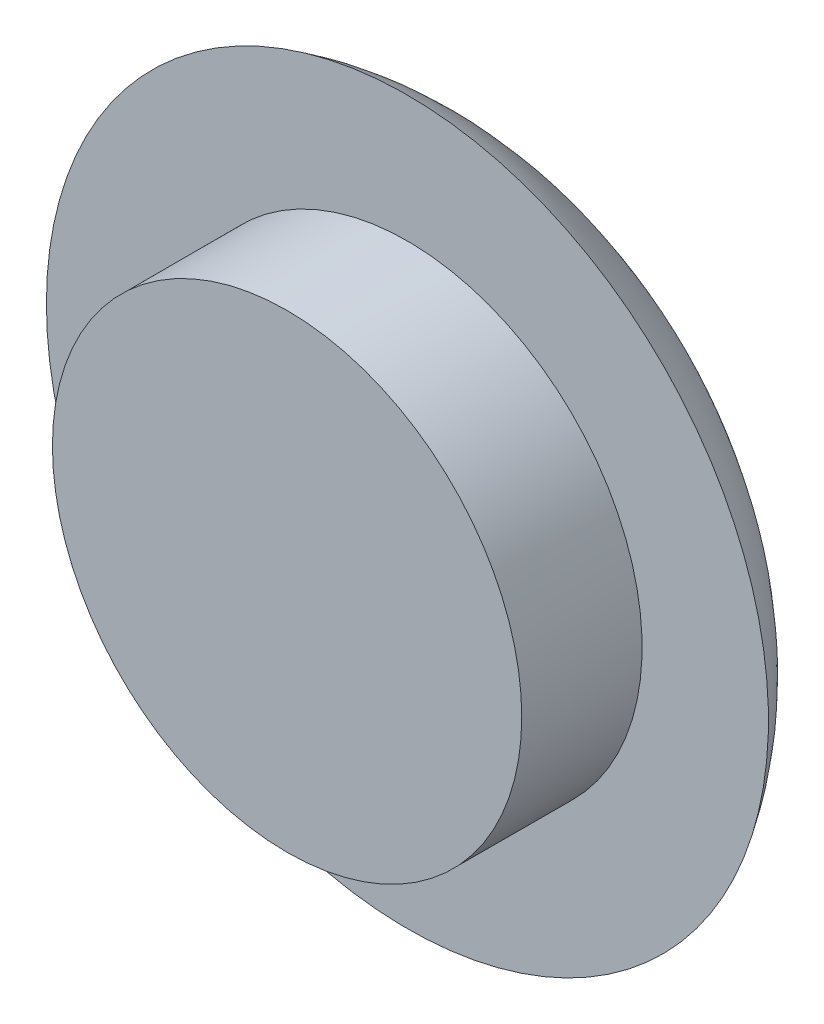
SolidWorks part; units mm, degrees
ref_plane "Front Plane" through (0, 0, 0) normal (0, 0, 1) x (1, 0, 0)
ref_plane "Top Plane" through (0, 0, 0) normal (0, 1, 0) x (1, 0, 0)
ref_plane "Right Plane" through (0, 0, 0) normal (1, 0, 0) x (0, 0, -1)
sketch "Sketch1" plane through (0, 0, 0) normal (0, 0, 1) x (1, 0, 0)
  circle A0 centre (0, 0) radius 2.925
  dimension "D1" = 5.85
extrude "Boss-Extrude1" add sketch "Sketch1" along normal blind 1.5
sketch "Sketch2" plane through (0, 0, 0) normal (0, 1, 0) x (1, 0, 0)
  line L0 (0, 1.4) -> (2, 1.4)
  line L1 (0, 1.4) -> (0, 0)
  line L2 (0, 0) -> (4.5, 0)
  arc A0 (2, 1.4) -> (4.5, 0) centre (2, -1.5321) cw
  dimension "D1" = 4.5
  dimension "D2" = 1.4
  dimension "D3" = 2
revolve "Revolve1" add sketch "Sketch2" angle 360 about L1
